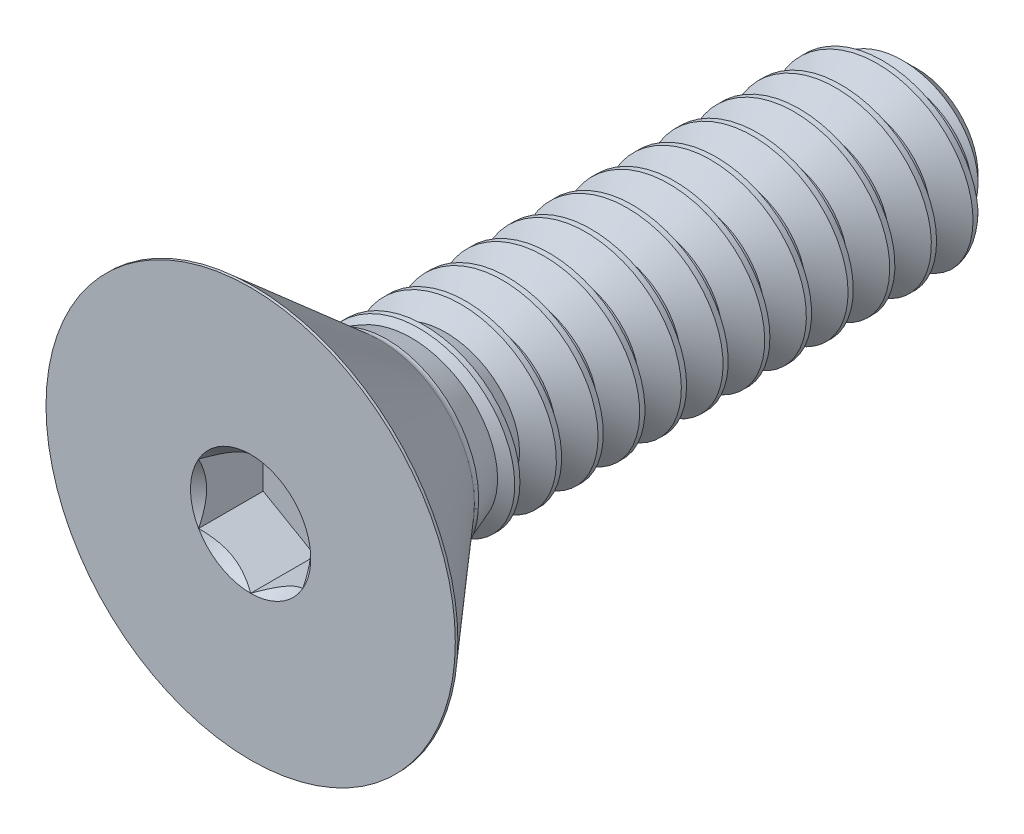
SolidWorks part; units mm, degrees
ref_plane "Front Plane" through (0, 0, 0) normal (0, 0, 1) x (1, 0, 0)
ref_plane "Top Plane" through (0, 0, 0) normal (0, 1, 0) x (1, 0, 0)
ref_plane "Right Plane" through (0, 0, 0) normal (1, 0, 0) x (0, 0, -1)
sketch "Sketch1" plane through (0, 0, 0) normal (1, 0, 0) x (0, 0, -1)
  line L0 (-6.35, 0) -> (6.35, 0) construction
  line L1 (-6.35, 0) -> (-6.35, 3.8989)
  line L2 (-6.35, 3.8989) -> (-6.3007, 3.8989)
  line L3 (-6.3007, 3.8989) -> (-3.8862, 1.8)
  line L4 (-6.3007, -3.8989) -> (-3.8862, -1.8)
  line L5 (6.35, 0) -> (6.35, 1.7526)
  line L6 (6.35, 1.7526) -> (-3.8862, 1.7526)
  line L7 (5.7547, 1.7526) -> (6.35, 1.1573)
  line L8 (6.3004, 1.8385) -> (6.6973, 1.1511) construction
  line L9 (6.6973, 1.1511) -> (7.0941, 1.8385) construction
  line L10 (7.0941, 1.8385) -> (6.3004, 1.8385) construction
  line L11 (6.3252, 1.7956) -> (7.0693, 1.7956)
  line L12 (7.0693, 1.7956) -> (6.7469, 1.237)
  line L13 (6.7469, 1.237) -> (6.6477, 1.237)
  line L14 (6.6477, 1.237) -> (6.3252, 1.7956)
  line L15 (6.6973, 1.237) -> (6.6973, 1.1511) construction
  line L16 (6.35, 1.7526) -> (7.0445, 1.7526) construction
  line L17 (6.6973, 1.8385) -> (6.6973, 1.7526) construction
  line L18 (6.35, -1.7526) -> (-3.8862, -1.7526)
  arc A0 (-3.8862, 1.8) -> (-3.7595, 1.7526) centre (-3.7595, 1.9458) ccw
  point P2 (0, 0)
  point P23 (-5.1181, 0)
  point P27 (6.6973, 1.7956)
  point P30 (5.1594, -1.7526)
  point P34 (-6.3007, -3.8989)
  dimension "Length" = 12.7
  dimension "Head Height" = 2.4638
  dimension "Head Diameter" = 7.7978
  dimension "Countersink Angle" = 82
  dimension "Thread Diameter" = 3.5052
  dimension "D2" = 0.0493
  dimension "Pitch" = 0.7937
  dimension "D4" = 0.0992
  dimension "D3" = 45
  dimension "D5" = 0.5953
  dimension "D6" = 1.2319
  dimension "D1" = 1.1906
sketch "Sketch2" plane through (0, 0, 0) normal (0, 0, 1) x (1, 0, 0)
  line L1 (0, 1.1457) -> (-0.9922, 0.5728)
  line L2 (-0.9922, 0.5728) -> (-0.9922, -0.5728)
  line L3 (-0.9922, -0.5728) -> (0, -1.1457)
  line L4 (0, -1.1457) -> (0.9922, -0.5728)
  line L5 (0.9922, -0.5728) -> (0.9922, 0.5728)
  line L6 (0.9922, 0.5728) -> (0, 1.1457)
  circle A0 centre (0, 0) radius 0.9922 construction
  dimension "Drive Size" = 1.9844
sketch "Sketch11" plane through (0, 0, 0) normal (1, 0, 0) x (0, 0, -1)
  line L0 (-6.3007, 3.8989) -> (-3.8862, 1.8) construction
  line L1 (-6.35, 0) -> (-6.35, 3.8989) construction
  line L2 (-6.3007, 3.8989) -> (-3.8862, 1.8)
  line L3 (-6.35, 0) -> (-6.35, 3.8989)
  line L4 (-6.35, 3.8989) -> (-6.3007, 3.8989) construction
  line L5 (-6.35, 3.8989) -> (-6.3007, 3.8989)
  line L6 (-3.7595, 1.7526) -> (5.7547, 1.7526)
  line L7 (5.7547, 1.7526) -> (6.35, 1.1573)
  line L8 (6.35, 1.1573) -> (6.35, 0)
  line L9 (6.35, 0) -> (-6.35, 0)
  arc A0 (-3.8862, 1.8) -> (-3.7595, 1.7526) centre (-3.7595, 1.9458) ccw construction
  arc A1 (-3.8862, 1.8) -> (-3.7595, 1.7526) centre (-3.7595, 1.9458) ccw
revolve "Revolve1" add sketch "Sketch11" angle 360 about L9
sketch "Sketch9" plane through (0, 0, 6.35) normal (0, 0, 1) x (1, 0, 0)
  line L0 (0.9922, -0.5728) -> (0.9922, 0.5728) construction
  line L1 (0, -1.1457) -> (0.9922, -0.5728) construction
  line L2 (-0.9922, -0.5728) -> (0, -1.1457) construction
  line L3 (-0.9922, 0.5728) -> (-0.9922, -0.5728) construction
  line L4 (0, 1.1457) -> (-0.9922, 0.5728) construction
  line L5 (0.9922, 0.5728) -> (0, 1.1457) construction
  line L6 (0.9922, -0.5728) -> (0.9922, 0.5728)
  line L7 (0, -1.1457) -> (0.9922, -0.5728)
  line L8 (-0.9922, -0.5728) -> (0, -1.1457)
  line L9 (-0.9922, 0.5728) -> (-0.9922, -0.5728)
  line L10 (0, 1.1457) -> (-0.9922, 0.5728)
  line L11 (0.9922, 0.5728) -> (0, 1.1457)
sketch "Sketch10" plane through (0, 0, 6.35) normal (0, 0, 1) x (1, 0, 0)
  circle A0 centre (0, 0) radius 1.1457
extrude "Cut-Extrude2" cut sketch "Sketch10" against normal up to vertex (1.2319 mm away) draft 45 up to point (0, 0, 5.1181)
extrude "Cut-Extrude1" cut sketch "Sketch9" against normal up to vertex (1.2319 mm away) up to point (0, 0, 5.1181)
ref_plane "Plane1" through (0, 0, 3.7595) normal (0, 0, 1) x (1, 0, 0)
split "Split1" trim tools "Plane1" bodies to split 111 resulting bodies 105 106
sketch "Sketch3" plane through (0, 0, -6.35) normal (0, 0, -1) x (-1, 0, 0)
  circle A0 centre (0, 0) radius 1.7526 construction
  circle A1 centre (0, 0) radius 1.7526
curve "Helix/Spiral1" pitch 0.7937 height 12.7 radius 1.7526 centre (0, 0, -6.35) axis (0, 0, 1) start towards (0, 1, 0)
sketch "Sketch4" plane through (0, 0, 0) normal (1, 0, 0) x (0, 0, -1)
  line L0 (6.3252, 1.7956) -> (7.0693, 1.7956) construction
  line L1 (6.6477, 1.237) -> (6.3252, 1.7956) construction
  line L2 (6.7469, 1.237) -> (6.6477, 1.237) construction
  line L3 (7.0693, 1.7956) -> (6.7469, 1.237) construction
  line L4 (6.3252, 1.7956) -> (7.0693, 1.7956)
  line L5 (6.6477, 1.237) -> (6.3252, 1.7956)
  line L6 (6.7469, 1.237) -> (6.6477, 1.237)
  line L7 (7.0693, 1.7956) -> (6.7469, 1.237)
sweep "Cut-Sweep1" cut profiles "Sketch4" path "Helix/Spiral1" align with end faces yes
sketch "Sketch7" plane through (0, 0, 3.7595) normal (0, 0, 1) x (1, 0, 0)
  circle A0 centre (0, 0) radius 1.7526
extrude "Boss-Extrude2" add sketch "Sketch7" against normal up to next (10.1095 mm away) draft 20
equation "\"D2@Sketch1\"=\"Head Height@Sketch1\"/50"
equation "\"D4@Sketch1\" = \"Pitch@Sketch1\" / 8"
equation "\"D5@Sketch1\"=\"Pitch@Sketch1\"*0.75"
equation "\"D4@Helix/Spiral1\"=\"Pitch@Sketch1\""
equation "\"D3@Helix/Spiral1\"=\"Length@Sketch1\""
equation "\"D6@Sketch1\"=\"Head Height@Sketch1\"/2"
equation "\"D1@Sketch1\"=\"Pitch@Sketch1\"*1.5"
